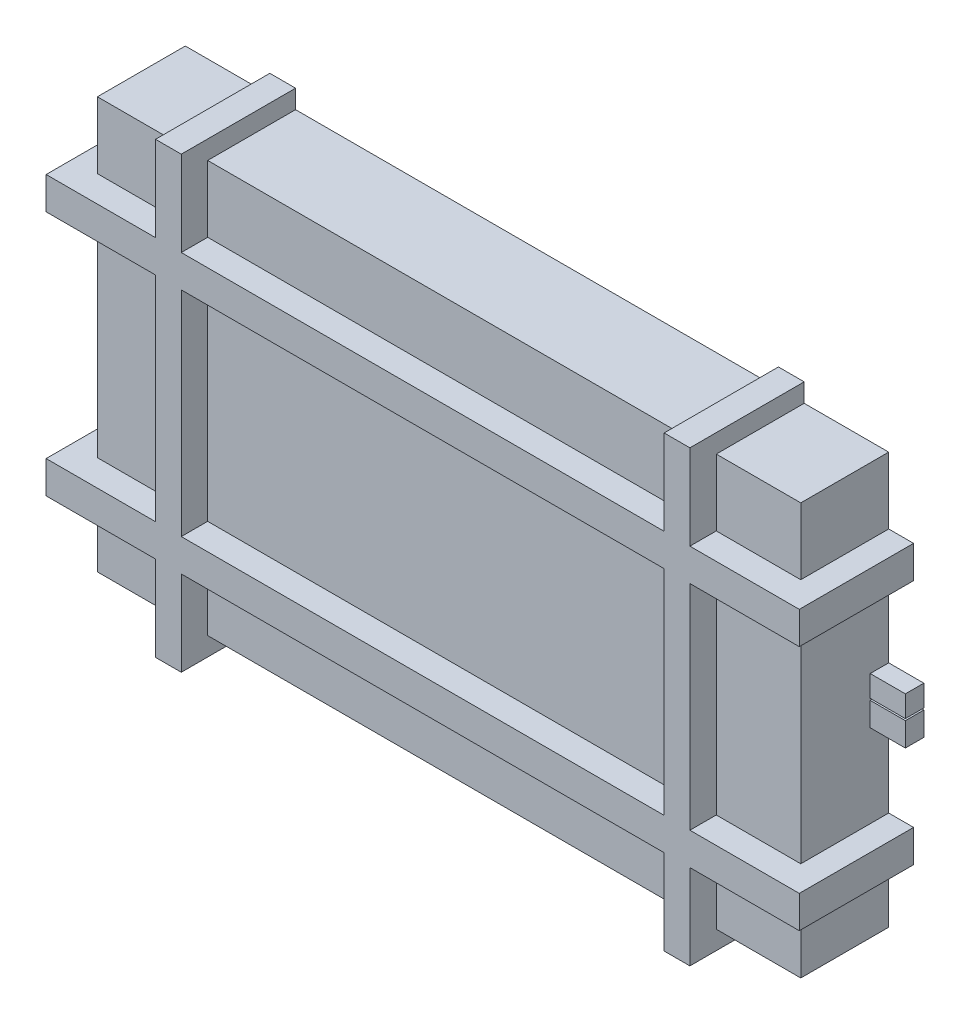
SolidWorks part; units mm, degrees
ref_plane "Front Plane" through (0, 0, 0) normal (0, 0, 1) x (1, 0, 0)
ref_plane "Top Plane" through (0, 0, 0) normal (0, 1, 0) x (1, 0, 0)
ref_plane "Right Plane" through (0, 0, 0) normal (1, 0, 0) x (0, 0, -1)
sketch "Sketch1" plane through (0, 0, 0) normal (0, 0, 1) x (1, 0, 0)
  line L1 (-25.4, -14.859) -> (25.4, -14.859)
  line L2 (-25.4, -14.859) -> (-25.4, 14.859)
  line L3 (-25.4, 14.859) -> (25.4, 14.859)
  line L4 (25.4, -14.859) -> (25.4, 14.859)
  line L5 (-25.4, -14.859) -> (25.4, 14.859) construction
  line L6 (-25.4, 14.859) -> (25.4, -14.859) construction
  point P0 (0, 0)
  dimension "D1" = 50.8
  dimension "D2" = 29.718
extrude "Boss-Extrude1" add sketch "Sketch1" along normal blind 6.35
sketch "Sketch2" plane through (25.4, 0, 0) normal (1, 0, 0) x (0, 0, -1)
  line L0 (0, -14.859) -> (0, 14.859) construction
  line L1 (0, 0) -> (-1.3376, 0)
  line L2 (0, 0) -> (0, -1.7137)
  line L3 (0, -1.7137) -> (-1.3376, -1.7137)
  line L4 (-1.3376, 0) -> (-1.3376, -1.7137)
extrude "Boss-Extrude2" add sketch "Sketch2" along normal blind 2.54
sketch "Sketch3" plane through (25.4, 0, 0) normal (1, 0, 0) x (0, 0, -1)
  line L0 (-1.3376, 0) -> (-1.3376, -1.7137) construction
  line L1 (0, 0.1273) -> (-1.3376, 0.1273)
  line L2 (0, 0.1273) -> (0, 1.6777)
  line L3 (0, 1.6777) -> (-1.3376, 1.6777)
  line L4 (-1.3376, 0.1273) -> (-1.3376, 1.6777)
  line L5 (0, 0) -> (0, 14.859) construction
extrude "Boss-Extrude3" add sketch "Sketch3" along normal blind 2.54
sketch "Sketch4" plane through (0, 0, 6.35) normal (0, 0, 1) x (1, 0, 0)
  line L1 (0, 0) -> (0, -8.8832) construction
  line L2 (-27.1971, -10.0509) -> (27.1971, -10.0509)
  line L3 (-27.1971, -10.0509) -> (-27.1971, -7.7155)
  line L4 (-27.1971, -7.7155) -> (27.1971, -7.7155)
  line L5 (27.1971, -10.0509) -> (27.1971, -7.7155)
  line L6 (-27.1971, -10.0509) -> (27.1971, -7.7155) construction
  line L7 (-27.1971, -7.7155) -> (27.1971, -10.0509) construction
extrude "Boss-Extrude4" add sketch "Sketch4" along normal blind 1.905 and the other way up to surface (6.35 mm away) other way up to face at (17.9917, -1.087, 0)
mirror "Mirror1" about plane through (0, 0, 0) normal (0, 1, 0) of "Boss-Extrude4"
sketch "Sketch5" plane through (0, 0, 6.35) normal (0, 0, 1) x (1, 0, 0)
  line L0 (0, 0) -> (18.3663, 0) construction
  line L2 (17.4361, 16.203) -> (19.2966, 16.203)
  line L3 (17.4361, 16.203) -> (17.4361, -16.203)
  line L4 (17.4361, -16.203) -> (19.2966, -16.203)
  line L5 (19.2966, 16.203) -> (19.2966, -16.203)
  line L6 (17.4361, 16.203) -> (19.2966, -16.203) construction
  line L7 (17.4361, -16.203) -> (19.2966, 16.203) construction
extrude "Boss-Extrude5" add sketch "Sketch5" along normal blind 1.905 and the other way up to surface (6.35 mm away) other way up to face at (7.7107, -0.3825, 0)
mirror "Mirror2" about plane through (0, 0, 0) normal (1, 0, 0) of "Boss-Extrude5"
